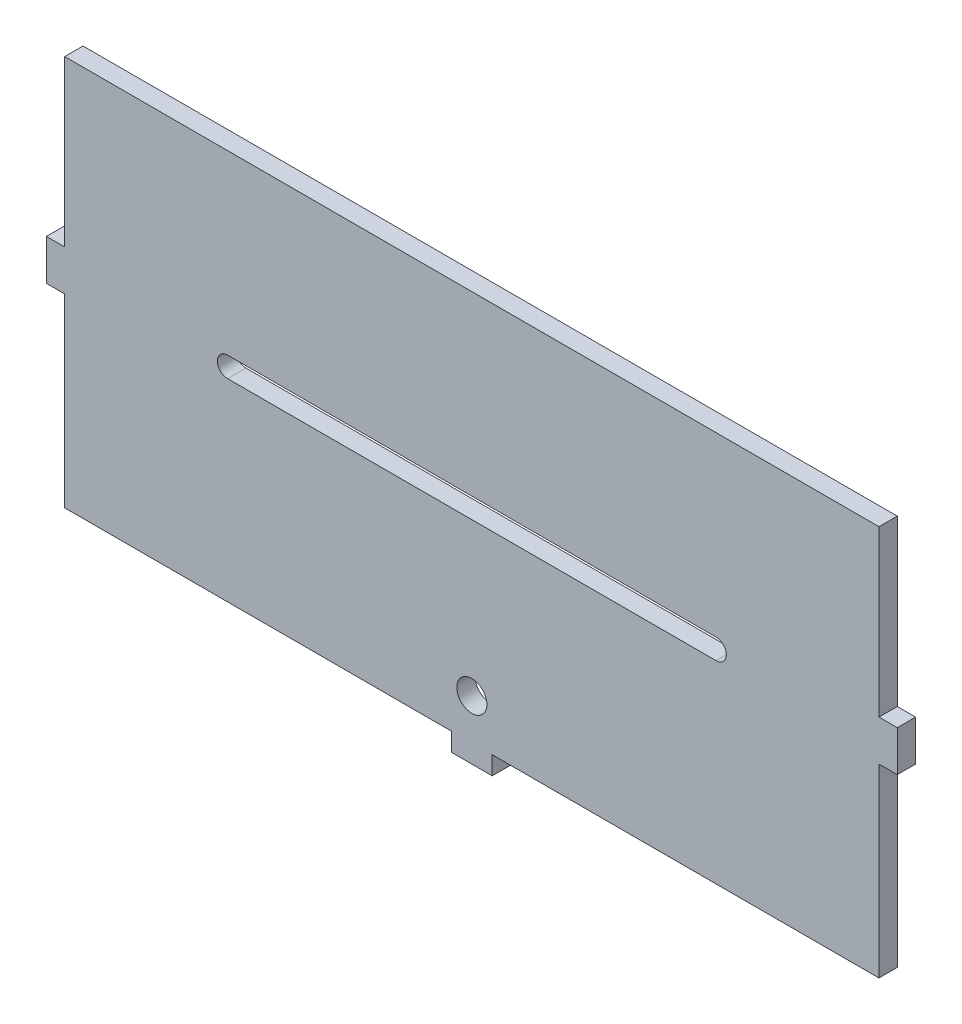
SolidWorks part; units mm, degrees
ref_plane "Front Plane" through (0, 0, 0) normal (0, 0, 1) x (1, 0, 0)
ref_plane "Top Plane" through (0, 0, 0) normal (0, 1, 0) x (1, 0, 0)
ref_plane "Right Plane" through (0, 0, 0) normal (1, 0, 0) x (0, 0, -1)
sketch "Sketch1" plane through (0, 0, 0) normal (0, 0, 1) x (1, 0, 0)
  line L0 (6.35, -63.5) -> (127, -63.5)
  line L1 (-127, -63.5) -> (-6.35, -63.5)
  line L2 (-127, -63.5) -> (-127, -5.715)
  line L3 (-127, 63.5) -> (127, 63.5)
  line L4 (127, -63.5) -> (127, -5.715)
  line L5 (-127, -63.5) -> (127, 63.5) construction
  line L6 (-127, 63.5) -> (127, -63.5) construction
  line L7 (-6.35, -69.215) -> (6.35, -69.215)
  line L8 (-6.35, -69.215) -> (-6.35, -63.5)
  line L10 (6.35, -69.215) -> (6.35, -63.5)
  line L11 (-127, 6.985) -> (-127, 63.5)
  line L12 (-132.715, -5.715) -> (-127, -5.715)
  line L13 (-132.715, -5.715) -> (-132.715, 6.985)
  line L14 (-132.715, 6.985) -> (-127, 6.985)
  line L16 (0, -55) -> (0, 55) construction
  line L17 (132.715, -5.715) -> (127, -5.715)
  line L18 (132.715, -5.715) -> (132.715, 6.985)
  line L19 (132.715, 6.985) -> (127, 6.985)
  line L20 (127, 6.985) -> (127, 63.5)
  point P0 (0, 0)
  point P6 (0, -63.5)
  point P10 (-127, 0)
  dimension "D1" = 127
  dimension "D2" = 254
  dimension "D3" = 12.7
  dimension "D4" = 5.715
  dimension "D5" = 12.7
  dimension "D6" = 57.785
extrude "Boss-Extrude1" add sketch "Sketch1" along normal blind 5.715
sketch "Sketch2" plane through (0, 0, 5.715) normal (0, 0, 1) x (1, 0, 0)
  line L0 (76.2, 0) -> (-76.2, 0) construction
  line L1 (76.2, -3.175) -> (-76.2, -3.175)
  line L2 (76.2, 3.175) -> (-76.2, 3.175)
  arc A0 (76.2, -3.175) -> (76.2, 3.175) centre (76.2, 0) ccw
  arc A1 (-76.2, 3.175) -> (-76.2, -3.175) centre (-76.2, 0) ccw
  point P3 (0, 0)
  dimension "D1" = 152.4
  dimension "D2" = 6.35
extrude "Cut-Extrude1" cut sketch "Sketch2" against normal through all
sketch "Sketch4" plane through (0, 0, 5.715) normal (0, 0, 1) x (1, 0, 0)
  line L0 (6.35, -63.5) -> (127, -63.5) construction
  circle A0 centre (0, -50.8) radius 4.699
  dimension "D1" = 9.398
  dimension "D2" = 12.7
extrude "Cut-Extrude2" cut sketch "Sketch4" against normal through all both
sketch "Sketch5" plane through (0, 0, 5.715) normal (0, 0, 1) x (1, 0, 0)
  line L0 (-127, 58.42) -> (127, 58.42)
  line L1 (-127, 63.5) -> (-127, 6.985) construction
  line L2 (127, 6.985) -> (127, 63.5) construction
  line L3 (127, 63.5) -> (-127, 63.5) construction
  line L4 (-127, 58.42) -> (-127, 63.5)
  line L5 (-127, 63.5) -> (127, 63.5)
  line L6 (127, 63.5) -> (127, 58.42)
  dimension "D1" = 5.08
extrude "Cut-Extrude3" cut sketch "Sketch5" against normal through all
